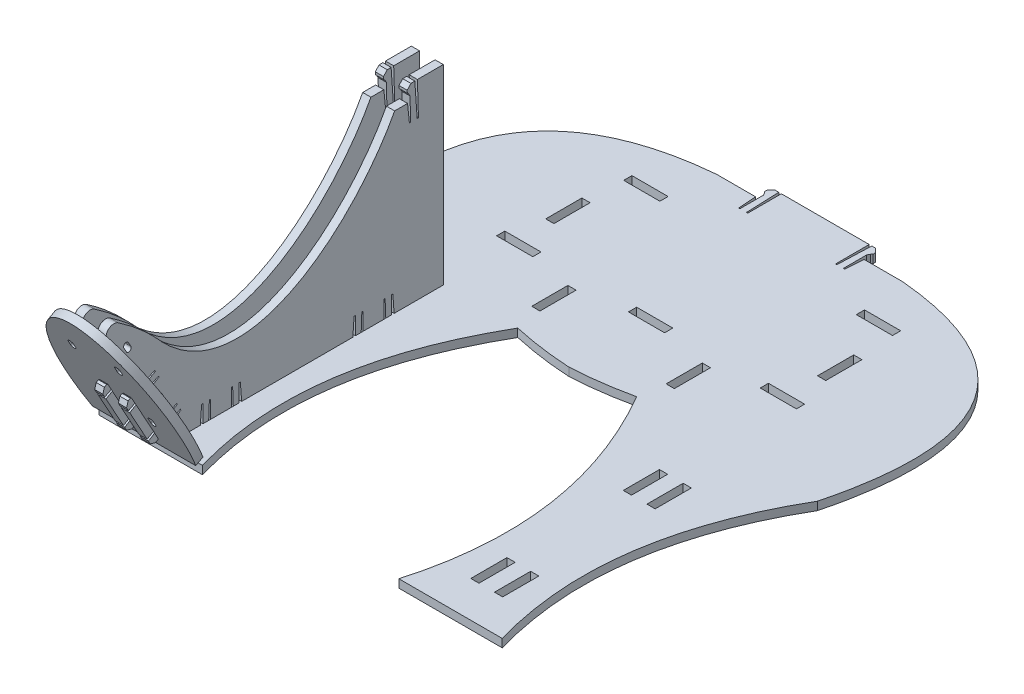
SolidWorks part; units mm, degrees
ref_plane "Front Plane" through (0, 0, 0) normal (0, 0, 1) x (1, 0, 0)
ref_plane "Top Plane" through (0, 0, 0) normal (0, 1, 0) x (1, 0, 0)
ref_plane "Right Plane" through (0, 0, 0) normal (1, 0, 0) x (0, 0, -1)
sketch "Sketch1" plane through (0, 0, 0) normal (0, 1, 0) x (1, 0, 0)
  line L0 (-20.25, -196.5319) -> (-60.25, -196.5319)
  line L1 (-75.25, -89.5319) -> (-5.25, -89.5319) construction
  line L2 (-40.25, -196.5319) -> (-40.25, -89.5319) construction
  line L3 (-43.25, -196.5319) -> (-43.25, -89.5319) construction
  line L4 (-37.25, -196.5319) -> (-37.25, -89.5319) construction
  line L5 (-37.25, -182.5319) -> (-37.25, -168.5319)
  line L6 (-37.25, -182.5319) -> (-34.075, -182.5319)
  line L7 (-37.25, -168.5319) -> (-34.075, -168.5319)
  line L8 (-34.075, -182.5319) -> (-34.075, -168.5319)
  line L9 (-46.425, -182.5319) -> (-46.425, -168.5319)
  line L10 (-46.425, -182.5319) -> (-43.25, -182.5319)
  line L11 (-46.425, -168.5319) -> (-43.25, -168.5319)
  line L12 (-43.25, -182.5319) -> (-43.25, -168.5319)
  line L13 (-46.425, -123.5319) -> (-46.425, -109.5319)
  line L14 (-46.425, -123.5319) -> (-43.25, -123.5319)
  line L15 (-46.425, -109.5319) -> (-43.25, -109.5319)
  line L16 (-43.25, -123.5319) -> (-43.25, -109.5319)
  line L17 (-34.075, -123.5319) -> (-34.075, -109.5319)
  line L18 (-34.075, -123.5319) -> (-37.25, -123.5319)
  line L19 (-34.075, -109.5319) -> (-37.25, -109.5319)
  line L20 (-37.25, -123.5319) -> (-37.25, -109.5319)
  line L22 (-3.25, 0.4681) -> (-18.25, 0.4681)
  line L27 (10.75, -62.7069) -> (17.75, -62.7069)
  line L28 (10.75, -62.7069) -> (10.75, -59.5319)
  line L29 (10.75, -59.5319) -> (17.75, -59.5319)
  line L30 (17.75, 6.4681) -> (17.75, -59.5319)
  line L32 (-34.25, -19.5319) -> (-20.25, -19.5319)
  line L33 (-34.25, -19.5319) -> (-34.25, -16.3569)
  line L34 (-34.25, -16.3569) -> (-20.25, -16.3569)
  line L35 (-20.25, -19.5319) -> (-20.25, -16.3569)
  line L39 (-33.25, -33.5319) -> (-36.425, -33.5319)
  line L40 (-33.25, -33.5319) -> (-33.25, -47.5319)
  line L41 (-33.25, -47.5319) -> (-36.425, -47.5319)
  line L42 (-36.425, -33.5319) -> (-36.425, -47.5319)
  line L43 (0.75, 6.4681) -> (17.75, 6.4681)
  line L47 (-40.25, -62.7069) -> (-26.25, -62.7069)
  line L48 (-40.25, -62.7069) -> (-40.25, -59.5319)
  line L49 (-40.25, -59.5319) -> (-26.25, -59.5319)
  line L50 (-26.25, -62.7069) -> (-26.25, -59.5319)
  line L51 (-105.3945, -19.5319) -> (97.5992, -19.5319) construction
  line L53 (95.3366, -59.5319) -> (-107.6571, -59.5319) construction
  line L54 (-6.6625, -65.5319) -> (-9.8375, -65.5319)
  line L55 (-6.6625, -65.5319) -> (-6.6625, -79.5319)
  line L56 (-6.6625, -79.5319) -> (-9.8375, -79.5319)
  line L57 (-9.8375, -65.5319) -> (-9.8375, -79.5319)
  line L58 (17.75, -62.7069) -> (17.75, -92.7069)
  line L59 (5.6087, -168.5319) -> (-89.1009, -168.5319) construction
  spline S0 degree 2 poles (-5.25, -89.5319) (6.1172, -92.0699) (17.75, -92.7069) knots 0 0 0 1 1 1
  spline S1 degree 2 poles (-18.25, 0.4681) (-96.8609, -6.5533) (-75.25, -89.5319) knots 0 0 0 1 1 1
  spline S2 degree 2 poles (-75.25, -89.5319) (-44.5969, -142.2068) (-60.25, -196.5319) knots 0 0 0 1 1 1
  spline S3 degree 2 poles (-5.25, -89.5319) (-35.9031, -142.2068) (-20.25, -196.5319) knots 0 0 0 1 1 1
  point P27 (-8.25, -79.5319)
  point P30 (0, 0)
  line B0 (0.75, 6.4681) -> (0.75, -6.5319)
  line B1 (0.75, -6.5319) -> (0.25, -6.5319)
  line B2 (0.25, -6.5319) -> (-0.25, 6.4681)
  line B3 (-0.25, 6.4681) -> (-1.75, 6.4681)
  line B4 (-1.75, 6.4681) -> (-3.25, 4.9681)
  line B5 (-3.25, 4.9681) -> (-3.25, 3.9681)
  line B6 (-3.25, 3.9681) -> (-2.75, 3.4681)
  line B7 (-2.75, 3.4681) -> (-2.25, 2.4681)
  line B8 (-2.25, 2.4681) -> (-2.25, -6.5319)
  line B9 (-2.25, -6.5319) -> (-2.75, -6.5319)
  line B10 (-2.75, -6.5319) -> (-3.25, 0.4681)
  dimension "D1" = 3
  dimension "D2" = 3
  dimension "D3" = 3.175
  dimension "D4" = 14
  dimension "D5" = 14
  dimension "D6" = 45
  dimension "D7" = 20
  dimension "D8" = 3.175
  dimension "D9" = 20
  dimension "D10" = 14
  dimension "D11" = 14
  dimension "D12" = 14
  dimension "D13" = 3.175
  dimension "D14" = 37
  dimension "D15" = 14
  dimension "D16" = 3.175
  dimension "D17" = 3.175
  dimension "D18" = 38
  dimension "D19" = 51
  dimension "D20" = 7
  dimension "D21" = 20
  dimension "D22" = 12
  dimension "D23" = 6
  dimension "D24" = 26
  dimension "D25" = 45
  dimension "D26" = 14
  dimension "D27" = 30
  dimension "D28" = 30
  dimension "D29" = 70
  dimension "D30" = 40
  dimension "D31" = 15
  dimension "D32" = 17
  dimension "D33" = 58
  dimension "D34" = 40
  dimension "D35" = 85
  dimension "D36" = 32
  dimension "D37" = 15
  dimension "D38" = 28
sketch_block_instance "Block-Snap-R-14"
sketch_block "Block-Snap-R" parameters "D1"=13, "D2"=0.5, "D3"=1, "D4"=0.5, "D5"=1, "D6"=2.5, "D7"=1.5, "D8"=1.5, "D9"=1.5, "D10"=1, "D11"=0.5, "D12"=1, "D13"=7
extrude "Boss-Extrude4" add sketch "Sketch1" along normal blind 3.175 contours B9 B10 L22 S1 S2 L0 S3 S0 L58 L27 L28 L29 L30 L43 B0 B1 B2 B3 B4 B5 B6 B7 B8 L18 L20 L19 L17 L8 L6 L5 L7 L12 L10 L9 L11 L16 L14 L13 L15 L35 L32 L33 L34 L42 L39 region at (-31.5874, 0, 76.7229)
mirror "Mirror1" about plane through (17.75, 3.175, 0) normal (1, 0, 0) of "Boss-Extrude4"
ref_plane "Plane1" through (-37.25, 0, 0) normal (1, 0, 0) x (0, 0, -1)
sketch "Sketch2" plane through (-37.25, 0, 0) normal (1, 0, 0) x (0, 0, -1)
  line L0 (-231.7529, 62.5492) -> (-197.4331, 0.1728) construction
  line L1 (-167.5319, 2.9477) -> (-124.5319, 2.9477)
  line L2 (-212.2199, 44.3022) -> (-211.2558, 42.55) construction
  line L3 (-183.5319, 2.9477) -> (-194.0319, 2.9477)
  line L4 (-108.5319, 2.9477) -> (-89.5319, 2.9477)
  line L5 (-210.8581, 21.0827) -> (-204.1093, 8.8168)
  line L6 (-207.5295, 27.4796) -> (-219.6487, 49.5064)
  line L7 (-196.9243, 8.2045) -> (-194.0319, 2.9477)
  line L8 (-89.5319, 2.9477) -> (-89.5319, 77.0684)
  line L9 (-99.5319, 77.0684) -> (-89.5319, 77.0684)
  line L10 (-199.2254, 39.5055) -> (-198.5996, 38.7256)
  line L11 (-103.3447, 70.9477) -> (-108.3447, 70.9477)
  line L12 (-211.3438, 44.7843) -> (-210.3796, 43.032)
  line L13 (-213.096, 43.8202) -> (-212.1319, 42.0679)
  line L14 (-199.2044, 20.6465) -> (-198.2403, 18.8942) construction
  line L15 (-198.3282, 21.1285) -> (-197.3641, 19.3762)
  line L16 (-200.0805, 20.1644) -> (-199.1164, 18.4121)
  line L17 (-207.4837, 14.9498) -> (-198.7223, 19.7703) construction
  line L18 (-196.5319, 3.175) -> (-196.5319, -40.8269) construction
  arc A0 (-215.3596, 53.451) -> (-219.6487, 49.5064) centre (-217.0203, 50.9526) ccw
  arc A1 (-211.3438, 44.7843) -> (-213.096, 43.8202) centre (-212.2199, 44.3022) ccw
  arc A2 (-212.1319, 42.0679) -> (-210.3796, 43.032) centre (-211.2558, 42.55) ccw
  arc A3 (-198.3282, 21.1285) -> (-200.0805, 20.1644) centre (-199.2044, 20.6465) ccw
  arc A4 (-199.1164, 18.4121) -> (-197.3641, 19.3762) centre (-198.2403, 18.8942) ccw
  spline S0 degree 3 poles (-198.5996, 38.7256) (-197.8882, 37.987) (-197.1577, 37.267) (-195.4744, 35.699) (-194.5145, 34.8665) (-191.5495, 32.4906) (-189.4594, 31.0681) (-186.6743, 29.5359) (-186.1086, 29.2418) (-184.9589, 28.6797) (-184.3778, 28.4133) (-182.6249, 27.6623) (-181.4397, 27.2242) (-177.834, 26.0998) (-175.3632, 25.6028) (-172.1887, 25.3068) (-171.5479, 25.2639) (-170.2719, 25.2113) (-169.6354, 25.2013) (-167.7301, 25.2187) (-166.4656, 25.2931) (-163.9473, 25.5581) (-162.6935, 25.7487) (-160.1957, 26.2385) (-158.9479, 26.5391) (-155.2769, 27.5764) (-152.9077, 28.4493) (-148.2947, 30.486) (-146.0512, 31.6503) (-142.7663, 33.5832) (-141.6837, 34.2597) (-139.5656, 35.6563) (-138.5273, 36.3781) (-135.469, 38.6074) (-133.5052, 40.1789) (-129.7089, 43.4703) (-127.8765, 45.1903) (-124.333, 48.7682) (-122.6221, 50.626) (-120.1453, 53.5142) (-119.3352, 54.4935) (-117.7563, 56.4725) (-116.986, 57.4737) (-114.7327, 60.5131) (-113.307, 62.5865) (-110.6782, 66.7409) (-109.4678, 68.8174) (-108.3447, 70.9477) knots 0.006162 0.006162 0.006162 0.006162 0.03125 0.03125 0.0625 0.0625 0.125 0.125 0.140625 0.140625 0.15625 0.15625 0.1875 0.1875 0.25 0.25 0.265625 0.265625 0.28125 0.28125 0.3125 0.3125 0.34375 0.34375 0.375 0.375 0.4375 0.4375 0.5 0.5 0.53125 0.53125 0.5625 0.5625 0.625 0.625 0.6875 0.6875 0.75 0.75 0.78125 0.78125 0.8125 0.8125 0.875 0.875 0.934758 0.934758 0.934758 0.934758
  spline S1 degree 3 poles (-199.2254, 39.5055) (-201.5722, 42.07) (-204.0545, 44.5082) (-208.0027, 47.9556) (-209.3564, 49.0696) (-211.4486, 50.6831) (-212.1574, 51.2122) (-213.5874, 52.2436) (-214.3093, 52.7465) (-215.1452, 53.3081) (-215.2523, 53.3797) (-215.3596, 53.451) knots 0 0 0 0 0.25 0.25 0.375 0.375 0.4375 0.4375 0.5 0.5 0.509173 0.509173 0.509173 0.509173
  point P23 (-211.7378, 43.4261)
  point P28 (-198.7223, 19.7703)
  point P40 (-111.1942, 70.9477)
  line B0 (-120.5319, -3.0523) -> (-112.5319, -3.0523)
  line B1 (-112.5319, -3.0523) -> (-112.5319, 9.9477)
  line B2 (-112.5319, 9.9477) -> (-112.0319, 9.9477)
  line B3 (-112.0319, 9.9477) -> (-111.5319, -3.0523)
  line B4 (-111.5319, -3.0523) -> (-110.0319, -3.0523)
  line B5 (-110.0319, -3.0523) -> (-108.5319, -1.5523)
  line B6 (-108.5319, -1.5523) -> (-108.5319, -0.5523)
  line B7 (-108.5319, -0.5523) -> (-109.0319, -0.0523)
  line B8 (-109.0319, -0.0523) -> (-109.5319, 0.9477)
  line B9 (-109.5319, 0.9477) -> (-109.5319, 9.9477)
  line B10 (-109.5319, 9.9477) -> (-109.0319, 9.9477)
  line B11 (-109.0319, 9.9477) -> (-108.5319, 2.9477)
  line B12 (-116.5319, -3.0523) -> (-116.5319, 9.9477) construction
  line B13 (-124.0319, 9.9477) -> (-124.5319, 2.9477)
  line B14 (-123.5319, 9.9477) -> (-124.0319, 9.9477)
  line B15 (-123.5319, 0.9477) -> (-123.5319, 9.9477)
  line B16 (-124.0319, -0.0523) -> (-123.5319, 0.9477)
  line B17 (-124.5319, -0.5523) -> (-124.0319, -0.0523)
  line B18 (-124.5319, -1.5523) -> (-124.5319, -0.5523)
  line B19 (-123.0319, -3.0523) -> (-124.5319, -1.5523)
  line B20 (-121.5319, -3.0523) -> (-123.0319, -3.0523)
  line B21 (-120.5319, 9.9477) -> (-121.0319, 9.9477)
  line B22 (-121.0319, 9.9477) -> (-121.5319, -3.0523)
  line B23 (-120.5319, -3.0523) -> (-120.5319, 9.9477)
  line B24 (-179.5319, -3.0523) -> (-171.5319, -3.0523)
  line B25 (-171.5319, -3.0523) -> (-171.5319, 9.9477)
  line B26 (-171.5319, 9.9477) -> (-171.0319, 9.9477)
  line B27 (-171.0319, 9.9477) -> (-170.5319, -3.0523)
  line B28 (-170.5319, -3.0523) -> (-169.0319, -3.0523)
  line B29 (-169.0319, -3.0523) -> (-167.5319, -1.5523)
  line B30 (-167.5319, -1.5523) -> (-167.5319, -0.5523)
  line B31 (-167.5319, -0.5523) -> (-168.0319, -0.0523)
  line B32 (-168.0319, -0.0523) -> (-168.5319, 0.9477)
  line B33 (-168.5319, 0.9477) -> (-168.5319, 9.9477)
  line B34 (-168.5319, 9.9477) -> (-168.0319, 9.9477)
  line B35 (-168.0319, 9.9477) -> (-167.5319, 2.9477)
  line B36 (-175.5319, -3.0523) -> (-175.5319, 9.9477) construction
  line B37 (-183.0319, 9.9477) -> (-183.5319, 2.9477)
  line B38 (-182.5319, 9.9477) -> (-183.0319, 9.9477)
  line B39 (-182.5319, 0.9477) -> (-182.5319, 9.9477)
  line B40 (-183.0319, -0.0523) -> (-182.5319, 0.9477)
  line B41 (-183.5319, -0.5523) -> (-183.0319, -0.0523)
  line B42 (-183.5319, -1.5523) -> (-183.5319, -0.5523)
  line B43 (-182.0319, -3.0523) -> (-183.5319, -1.5523)
  line B44 (-180.5319, -3.0523) -> (-182.0319, -3.0523)
  line B45 (-179.5319, 9.9477) -> (-180.0319, 9.9477)
  line B46 (-180.0319, 9.9477) -> (-180.5319, -3.0523)
  line B47 (-179.5319, -3.0523) -> (-179.5319, 9.9477)
  line B48 (-201.1555, 30.416) -> (-207.5295, 27.4796)
  line B49 (-200.9145, 29.9779) -> (-201.1555, 30.416)
  line B50 (-208.7997, 25.6394) -> (-200.9145, 29.9779)
  line B51 (-209.9169, 25.5954) -> (-208.7997, 25.6394)
  line B52 (-210.596, 25.7924) -> (-209.9169, 25.5954)
  line B53 (-211.4721, 25.3104) -> (-210.596, 25.7924)
  line B54 (-212.0633, 23.2731) -> (-211.4721, 25.3104)
  line B55 (-211.3402, 21.9589) -> (-212.0633, 23.2731)
  line B56 (-199.4683, 27.3495) -> (-199.7093, 27.7875)
  line B57 (-199.7093, 27.7875) -> (-211.3402, 21.9589)
  line B58 (-210.8581, 21.0827) -> (-199.4683, 27.3495)
  line B59 (-204.1093, 8.8168) -> (-192.7195, 15.0835)
  line B60 (-192.7195, 15.0835) -> (-192.4785, 14.6454)
  line B61 (-192.4785, 14.6454) -> (-203.6273, 7.9406)
  line B62 (-203.6273, 7.9406) -> (-202.9042, 6.6264)
  line B63 (-202.9042, 6.6264) -> (-200.8669, 6.0353)
  line B64 (-200.8669, 6.0353) -> (-199.9908, 6.5174)
  line B65 (-199.9908, 6.5174) -> (-199.7937, 7.1965)
  line B66 (-199.7937, 7.1965) -> (-199.1586, 8.1166)
  line B67 (-199.1586, 8.1166) -> (-191.2733, 12.4551)
  line B68 (-191.2733, 12.4551) -> (-191.0323, 12.017)
  line B69 (-191.0323, 12.017) -> (-196.9243, 8.2045)
  line B70 (-99.5319, 77.0684) -> (-99.1304, 64.0746)
  line B71 (-99.1304, 64.0746) -> (-99.6302, 64.0591)
  line B72 (-99.6302, 64.0591) -> (-100.5315, 77.0375)
  line B73 (-100.5315, 77.0375) -> (-102.0307, 76.9912)
  line B74 (-102.0307, 76.9912) -> (-103.4837, 75.4456)
  line B75 (-103.4837, 75.4456) -> (-103.4528, 74.446)
  line B76 (-103.4528, 74.446) -> (-102.9376, 73.9617)
  line B77 (-102.9376, 73.9617) -> (-102.407, 72.9776)
  line B78 (-102.407, 72.9776) -> (-102.129, 63.9819)
  line B79 (-102.129, 63.9819) -> (-102.6288, 63.9665)
  line B80 (-102.6288, 63.9665) -> (-103.3447, 70.9477)
  dimension "D2" = 3
  dimension "D1" = 6
  dimension "D3" = 1
  dimension "D4" = 68
  dimension "D5" = 2
  dimension "D6" = 4
  dimension "D7" = 4
  dimension "D8" = 26
  dimension "D9" = 10.5
  dimension "D10" = 45
  dimension "D11" = 2.5
  dimension "D12" = 20
  dimension "D13" = 10
  dimension "D14" = 5
sketch_block_instance "Block-Snap-14mm-2"
sketch_block "Block-Snap-14mm" parameters "D1"=8, "D2"=13, "D3"=0.5, "D4"=1, "D5"=0.5, "D6"=1, "D7"=2.5, "D8"=1.5, "D9"=1.5, "D10"=1.5, "D11"=1, "D12"=0.5, "D13"=1, "D14"=7
sketch_block_instance "Block-Snap-14mm-3"
sketch_block_instance "Block-Snap-L-1"
sketch_block "Block-Snap-L" parameters "D1"=13, "D2"=0.5, "D3"=1, "D4"=1.5, "D5"=1.5, "D6"=0.5, "D7"=1, "D8"=7, "D9"=1, "D10"=0.5, "D11"=1, "D12"=1.5, "D13"=2.5
sketch_block_instance "Block-Snap-R-15"
sketch_block_instance "Block-Snap-R-16"
extrude "Boss-Extrude5" add sketch "Sketch2" along normal blind 3.175 contours B79 B80 L11 S0 L10 S1 A0 L6 B48 B49 B50 B51 B52 B53 B54 B55 B57 B56 B58 L5 B59 B60 B61 B62 B63 B64 B65 B66 B67 B68 B69 L7 L3 B37 B38 B39 B40 B41 B42 B43 B44 B46 B45 B47 B24 B25 B26 B27 B28 B29 B30 region at (-37.25, 26.9869, 138.6326)
ref_plane "Plane2" through (-40.25, 0, 0) normal (1, 0, 0) x (0, 0, -1)
mirror "Mirror2" about plane through (-40.25, 0, 0) normal (1, 0, 0) of "Boss-Extrude5"
ref_plane "Plane3" through (0, -81.2642, 147.6982) normal (0, -0.4821, 0.8761) x (1, 0, 0)
ref_point "Point1"
ref_point "Point2"
ref_axis "Axis1" through (-37.25, 26.6035, 207.0474) along (-1, 0, 0)
sketch "Sketch3" plane through (0, -81.2642, 147.6982) normal (0, -0.4821, 0.8761) x (1, 0, 0)
  line L0 (-61.7701, 97.7155) -> (-21.7701, 97.7155)
  line L1 (-31.25, 141.0891) -> (-31.25, 139.0891) construction
  line L2 (-46.425, 123.1169) -> (-46.425, 103.1169)
  line L3 (-46.425, 123.1169) -> (-43.25, 123.1169)
  line L4 (-46.425, 103.1169) -> (-43.25, 103.1169)
  line L5 (-43.25, 123.1169) -> (-43.25, 103.1169)
  line L6 (-37.25, 123.1169) -> (-37.25, 103.1169)
  line L7 (-37.25, 123.1169) -> (-34.075, 123.1169)
  line L8 (-37.25, 103.1169) -> (-34.075, 103.1169)
  line L9 (-34.075, 123.1169) -> (-34.075, 103.1169)
  line L10 (-30.25, 141.0891) -> (-30.25, 139.0891)
  line L11 (-32.25, 141.0891) -> (-32.25, 139.0891)
  line L12 (-31.25, 114.0891) -> (-31.25, 112.0891) construction
  line L13 (-30.25, 114.0891) -> (-30.25, 112.0891)
  line L14 (-32.25, 114.0891) -> (-32.25, 112.0891)
  line L15 (-37.25, 123.1169) -> (-43.25, 123.1169) construction
  line L16 (-40.25, 121.8519) -> (-40.25, 134.9724) construction
  line L17 (-49.25, 114.0891) -> (-49.25, 112.0891) construction
  line L18 (-50.25, 114.0891) -> (-50.25, 112.0891)
  line L19 (-48.25, 114.0891) -> (-48.25, 112.0891)
  line L20 (-49.25, 141.0891) -> (-49.25, 139.0891) construction
  line L21 (-50.25, 141.0891) -> (-50.25, 139.0891)
  line L22 (-48.25, 141.0891) -> (-48.25, 139.0891)
  line L23 (-37.25, 123.1169) -> (-43.25, 123.1169) construction
  line L25 (-37.25, 96.3763) -> (-37.25, 91.2466) construction
  arc A0 (-30.25, 141.0891) -> (-32.25, 141.0891) centre (-31.25, 141.0891) ccw
  arc A1 (-32.25, 139.0891) -> (-30.25, 139.0891) centre (-31.25, 139.0891) ccw
  arc A2 (-30.25, 114.0891) -> (-32.25, 114.0891) centre (-31.25, 114.0891) ccw
  arc A3 (-32.25, 112.0891) -> (-30.25, 112.0891) centre (-31.25, 112.0891) ccw
  arc A4 (-50.25, 114.0891) -> (-48.25, 114.0891) centre (-49.25, 114.0891) cw
  arc A5 (-48.25, 112.0891) -> (-50.25, 112.0891) centre (-49.25, 112.0891) cw
  arc A6 (-50.25, 141.0891) -> (-48.25, 141.0891) centre (-49.25, 141.0891) cw
  arc A7 (-48.25, 139.0891) -> (-50.25, 139.0891) centre (-49.25, 139.0891) cw
  spline S0 degree 3 poles (-21.7701, 97.7155) (-21.4377, 99.0951) (-21.1511, 100.4831) (-20.3777, 104.8819) (-20.0423, 107.9201) (-19.8505, 111.7589) (-19.8237, 112.5285) (-19.7933, 114.0629) (-19.7895, 114.8288) (-19.8125, 117.1226) (-19.8731, 118.6466) (-20.1916, 123.2032) (-20.5838, 126.2205) (-21.4717, 130.7124) (-21.818, 132.2039) (-22.4219, 134.4317) (-22.6374, 135.173) (-23.0957, 136.642) (-23.3387, 137.371) (-24.1117, 139.5405) (-24.6854, 140.9635) (-25.6493, 143.0569) (-25.9879, 143.7478) (-26.7038, 145.1141) (-27.0804, 145.788) (-28.2627, 147.7622) (-29.123, 149.0218) (-31.031, 151.3945) (-32.0766, 152.509) (-33.5604, 153.7637) (-33.866, 154.0071) (-34.4885, 154.4709) (-34.8064, 154.6922) (-35.782, 155.3207) (-36.4614, 155.6932) (-37.8936, 156.3206) (-38.626, 156.5661) (-39.7507, 156.8203) (-40.1301, 156.886) (-40.8981, 156.9767) (-41.2891, 157.0018) (-42.4609, 157.0115) (-43.229, 156.9319) (-44.3633, 156.6945) (-44.7384, 156.5956) (-45.4828, 156.3597) (-45.8493, 156.2235) (-46.9197, 155.7707) (-47.6006, 155.4084) (-48.5823, 154.7914) (-48.9029, 154.5733) (-49.5317, 154.1145) (-49.8392, 153.8743) (-51.3296, 152.6371) (-52.3913, 151.524) (-53.851, 149.7291) (-54.316, 149.1076) (-55.2007, 147.8345) (-55.6185, 147.186) (-56.809, 145.2099) (-57.5194, 143.8521) (-58.8077, 141.0724) (-59.3853, 139.6502) (-60.1655, 137.4751) (-60.4116, 136.7416) (-60.8738, 135.2692) (-61.0899, 134.5307) (-61.6962, 132.3093) (-62.0447, 130.8201) (-62.9398, 126.3306) (-63.3378, 123.3084) (-63.6632, 118.7353) (-63.7259, 117.2042) (-63.7512, 114.8974) (-63.748, 114.1256) (-63.7187, 112.5859) (-63.6925, 111.818) (-63.5041, 107.9876) (-63.1721, 104.9528) (-62.3991, 100.531) (-62.1085, 99.1193) (-61.7701, 97.7155) knots 0.033462 0.033462 0.033462 0.033462 0.0625 0.0625 0.125 0.125 0.140625 0.140625 0.15625 0.15625 0.1875 0.1875 0.25 0.25 0.28125 0.28125 0.296875 0.296875 0.3125 0.3125 0.34375 0.34375 0.359375 0.359375 0.375 0.375 0.40625 0.40625 0.4375 0.4375 0.445312 0.445312 0.453125 0.453125 0.46875 0.46875 0.484375 0.484375 0.492187 0.492187 0.5 0.5 0.515625 0.515625 0.523437 0.523437 0.53125 0.53125 0.546875 0.546875 0.554687 0.554687 0.5625 0.5625 0.59375 0.59375 0.609375 0.609375 0.625 0.625 0.65625 0.65625 0.6875 0.6875 0.703125 0.703125 0.71875 0.71875 0.75 0.75 0.8125 0.8125 0.84375 0.84375 0.859375 0.859375 0.875 0.875 0.9375 0.9375 0.967022 0.967022 0.967022 0.967022
  point P12 (-31.25, 140.0891)
  point P17 (-31.25, 113.0891)
  point P25 (-40.25, 123.1169)
  point P29 (-49.25, 113.0891)
  point P36 (-49.25, 140.0891)
  point P41 (-31.25, 111.0891)
  point P42 (-31.25, 138.0891)
  point P43 (-31.25, 115.0891)
  dimension "D6" = 3
  dimension "D1" = 2
  dimension "D2" = 4
  dimension "D3" = 20
  dimension "D4" = 3.175
  dimension "D5" = 40
  dimension "D7" = 8
  dimension "D8" = 5.4014
  dimension "D9" = 13.3736
  dimension "D10" = 23
  dimension "D11" = 3.175
extrude "Boss-Extrude6" add sketch "Sketch3" along normal blind 3.175 contours L0 S0 L22 A7 L21 A6 L19 A5 L18 A4 L7 L9 L8 L6 L3 L5 L4 L2 A1 L11 A0 L10 A3 L14 A2 L13 region at (-41.8859, 27.7841, 207.697)
ref_plane "Plane4" through (0, 123.175, 0) normal (0, 1, 0) x (1, 0, 0)
